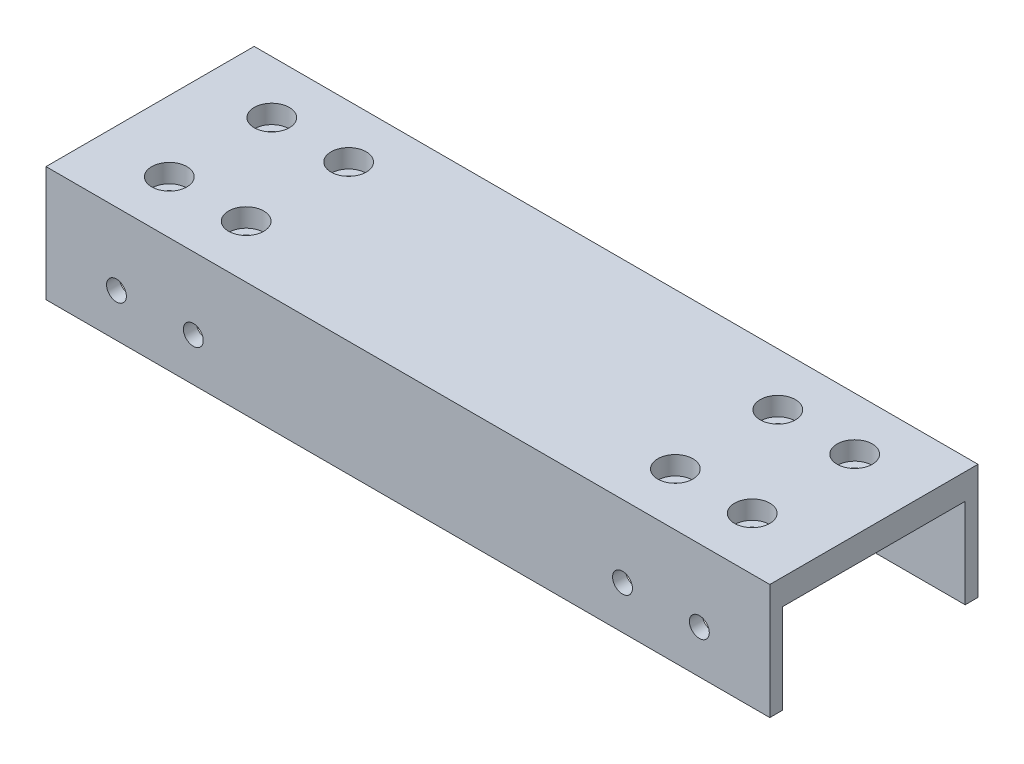
SolidWorks part; units mm, degrees
ref_plane "Front Plane" through (0, 0, 0) normal (0, 0, 1) x (1, 0, 0)
ref_plane "Top Plane" through (0, 0, 0) normal (0, 1, 0) x (1, 0, 0)
ref_plane "Right Plane" through (0, 0, 0) normal (1, 0, 0) x (0, 0, -1)
sketch "Sketch1" plane through (0, 0, 0) normal (0, 1, 0) x (1, 0, 0)
  line L1 (0, 0) -> (113, 0)
  line L2 (0, 0) -> (0, 32.5)
  line L3 (0, 32.5) -> (113, 32.5)
  line L4 (113, 0) -> (113, 32.5)
  dimension "D1" = 32.5
  dimension "D2" = 113
extrude "Boss-Extrude1" add sketch "Sketch1" along normal blind 4
sketch "Sketch4" plane through (0, 4, 0) normal (0, 1, 0) x (1, 0, 0)
  line L0 (56.5, 32.5) -> (56.5, -12.4802) construction
  line L1 (113, 32.5) -> (0, 32.5) construction
  line L3 (0, 16.25) -> (122.1673, 16.25) construction
  line L4 (0, 32.5) -> (0, 0) construction
  point P0 (11, 24.25)
  point P12 (23, 24.25)
  point P13 (23, 8.25)
  point P14 (11, 8.25)
  point P25 (102, 8.25)
  point P26 (90, 8.25)
  point P27 (90, 24.25)
  point P28 (102, 24.25)
  dimension "D1" = 2
  dimension "D3" = 12
  dimension "D4" = 16
  dimension "D5" = 8
  dimension "D6" = 79
  dimension "D2" = 2
hole_wizard "CBORE for M2.5 Hex Socket Head Cap Screw1" positions "Sketch4" profile "Sketch3" counterbore size "M2.5" standard "DIN" end condition through all
sketch "Sketch3" plane through (11, 4, -24.25) normal (1, 0, 0) x (0, 0, 1)
  line L0 (0, 0) -> (0, 4)
  line L1 (0, 4) -> (1.45, 4)
  line L3 (1.45, 4) -> (1.45, 2.9)
  line L4 (1.45, 2.9) -> (2.75, 2.9)
  line L5 (2.75, 2.9) -> (2.75, 0)
  line L7 (2.75, 0) -> (0, 0)
  line L11 (0, -6.35) -> (0, 107.95) construction
  dimension "Thru Hole Dia." = 2.9
  dimension "Thru Hole Depth" = 4
  dimension "C'Bore Dia." = 5.5
  dimension "C'Bore Depth" = 2.9
sketch "Sketch5" plane through (0, 0, 0) normal (0, -1, 0) x (1, 0, 0)
  line L0 (0, -16.25) -> (113, -16.25) construction
  line L1 (0, 0) -> (113, 0)
  line L3 (0, -32.5) -> (113, -32.5)
  line L5 (0, -2) -> (113, -2)
  line L7 (0, -30.5) -> (113, -30.5)
  line L9 (0, -16.25) -> (113, -16.25) construction
  line L20 (0, 0) -> (0, -2)
  line L23 (0, -32.5) -> (0, -30.5)
  line L24 (113, 0) -> (113, -2)
  line L25 (113, -30.5) -> (113, -32.5)
  dimension "D1" = 28.5
extrude "Boss-Extrude2" add sketch "Sketch5" along normal blind 14
sketch "Sketch7" plane through (0, -14, 0) normal (0, -1, 0) x (1, 0, 0)
  line L1 (0, -2) -> (113, -2) construction
  line L2 (34.5, -2) -> (78.5, -2)
  line L3 (34.5, -2) -> (34.5, -30.5)
  line L5 (113, -30.5) -> (0, -30.5) construction
  line L6 (34.5, -30.5) -> (78.5, -30.5)
  line L21 (78.5, -2) -> (78.5, -30.5)
  line L22 (113, -30.5) -> (0, -30.5) construction
  point P10 (56.5, -30.5)
  dimension "D1" = 44
extrude "Boss-Extrude3" add sketch "Sketch7" against normal up to next
sketch "Sketch10" plane through (0, 0, -32.5) normal (0, 0, -1) x (-1, 0, 0)
  line L1 (0, 0) -> (-34.5, 0) construction
  line L2 (-23, -7.25) -> (-11, -7.25)
  line L3 (-9.55, 1.1) -> (-12.45, 1.1) construction
  line L4 (-9.55, 1.1) -> (-12.45, 1.1)
  line L5 (-11, 1.1) -> (-11, -7.25)
  line L8 (-56.5, 4) -> (-56.5, -40.6573) construction
  line L9 (-113, 4) -> (0, 4) construction
  point P0 (-11, -7.25)
  point P2 (-23, -7.25)
  point P30 (-102, -7.25)
  point P31 (-90, -7.25)
  dimension "D1" = 7.25
  dimension "D2" = 12
hole_wizard "M2.5 Clearance Hole1" positions "Sketch10" profile "Sketch9" hole size "M2.5" standard "DIN" end condition through all
sketch "Sketch9" plane through (11, -7.25, -32.5) normal (1, 0, 0) x (0, 1, 0)
  line L0 (0, 0) -> (0, 32.5)
  line L1 (0, 32.5) -> (1.55, 32.5)
  line L2 (1.55, 32.5) -> (1.55, 0)
  line L5 (1.55, 0) -> (0, 0)
  line L11 (0, -6.35) -> (0, 107.95) construction
  dimension "Thru Hole Dia." = 3.1
  dimension "Thru Hole Depth" = 32.5
sketch "Sketch11" plane through (0, -14, 0) normal (0, -1, 0) x (1, 0, 0)
  line L24 (38.5, -4) -> (38.5, -28.5)
  line L25 (38.5, -28.5) -> (74.5, -28.5)
  line L26 (74.5, -28.5) -> (74.5, -4)
  line L27 (74.5, -4) -> (38.5, -4)
  line L28 (38.5, -4) -> (38.5, -28.5)
  line L29 (38.5, -28.5) -> (74.5, -28.5)
  line L30 (74.5, -28.5) -> (74.5, -4)
  line L31 (74.5, -4) -> (38.5, -4)
  dimension "D1" = 4
extrude "Cut-Extrude1" cut sketch "Sketch11" against normal blind 14
